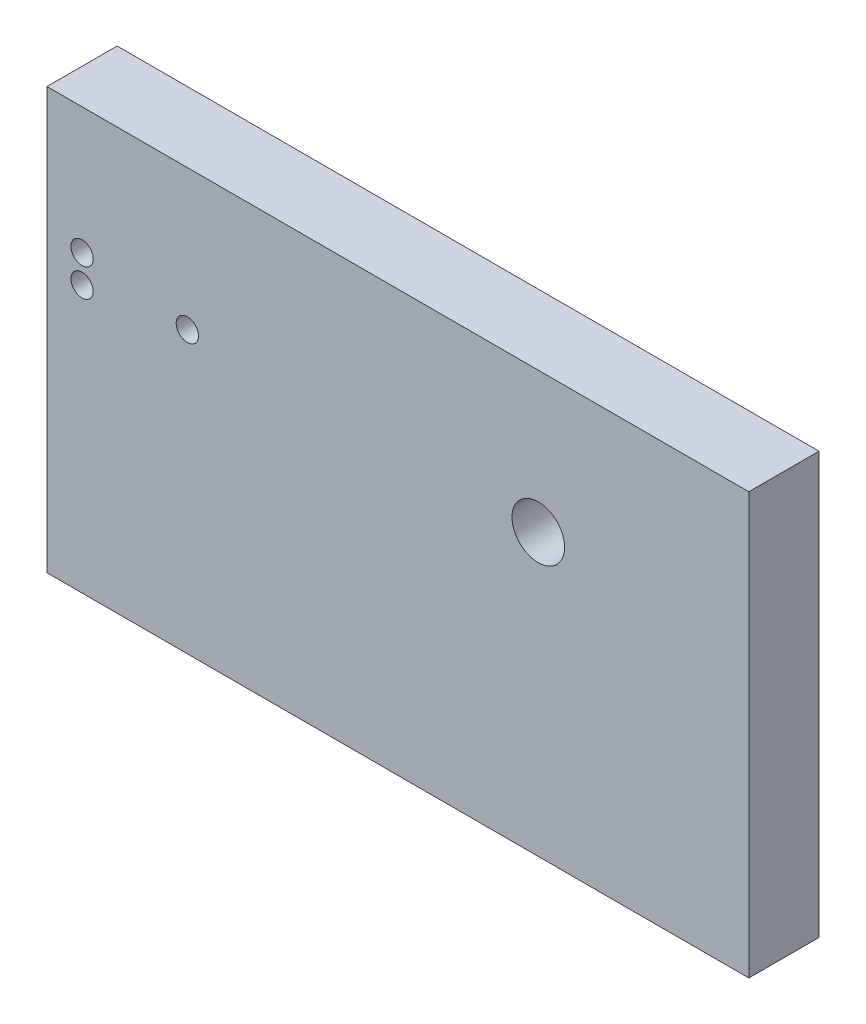
SolidWorks part; units mm, degrees
ref_plane "Front Plane" through (0, 0, 0) normal (0, 0, 1) x (1, 0, 0)
ref_plane "Top Plane" through (0, 0, 0) normal (0, 1, 0) x (1, 0, 0)
ref_plane "Right Plane" through (0, 0, 0) normal (1, 0, 0) x (0, 0, -1)
sketch "Sketch1" plane through (0, 0, 0) normal (0, 0, 1) x (1, 0, 0)
  line L1 (0, 0) -> (127, 0)
  line L2 (0, 0) -> (0, 76.2)
  line L3 (0, 76.2) -> (127, 76.2)
  line L4 (127, 0) -> (127, 76.2)
  dimension "D1" = 127
  dimension "D2" = 76.2
extrude "Boss-Extrude1" add sketch "Sketch1" along normal blind 12.7 contours L2 L1 L4 L3
hole_wizard "1/32 (0.159) Diameter Hole1" positions "Sketch5" profile "Sketch6" hole size "1/32" standard "ANSI Inch" end condition through all
sketch "Sketch5" plane through (0, 0, 12.7) normal (0, 0, 1) x (1, 0, 0)
  line L0 (0, 0) -> (0, 76.2) construction
  line L1 (0, 0) -> (127, 0) construction
  point P0 (25.4, 50.8)
  dimension "D1" = 25.4
  dimension "D2" = 50.8
sketch "Sketch6" plane through (25.4, 50.8, 12.7) normal (1, 0, 0) x (0, -1, 0)
  line L0 (0, 0) -> (0, 12.7)
  line L1 (0, 12.7) -> (2.0193, 12.7)
  line L2 (2.0193, 12.7) -> (2.0193, 0)
  line L5 (2.0193, 0) -> (0, 0)
  line L11 (0, -6.35) -> (0, 107.95) construction
  dimension "Thru Hole Dia." = 4.0386
  dimension "Thru Hole Depth" = 12.7
hole_wizard "#10-32 Tapped Hole1" positions "Sketch9" profile "Sketch10" tap size "#10-32" standard "ANSI Inch"
sketch "Sketch9" plane through (0, 0, 0) normal (0, -1, 0) x (-1, 0, 0)
  line L0 (0, -12.7) -> (-127, -12.7) construction
  line L1 (-19.05, -6.35) -> (-107.95, -6.35) construction
  line L3 (-63.5, -12.7) -> (-63.5, 0) construction
  line L4 (0, 0) -> (-127, 0) construction
  point P0 (-19.05, -6.35)
  point P2 (-107.95, -6.35)
  point P21 (-63.5, -6.35)
  dimension "D1" = 6.35
  dimension "D2" = 88.9
sketch "Sketch10" plane through (19.05, 0, 6.35) normal (1, 0, 0) x (0, 0, -1)
  line L0 (0, 0) -> (0, 13.9133)
  line L1 (0, 13.9133) -> (2.0193, 12.7)
  line L2 (2.0193, 12.7) -> (2.0193, 0)
  line L5 (2.0193, 0) -> (0, 0)
  line L10 (0, 13.9133) -> (-2.0193, 12.7) construction
  line L11 (0, -6.35) -> (0, 107.95) construction
  dimension "Tap Drill Dia." = 4.0386
  dimension "Tap Drill Depth" = 12.7
  dimension "Drill Angle" = 118
cosmetic thread "Hole Thread3" parameters "D1"=12.7, "D2"=4.826
cosmetic thread "Hole Thread4" parameters "D1"=12.7, "D2"=4.826
hole_wizard "3/8 (0.375) Diameter Hole1" positions "Sketch14" profile "Sketch15" hole size "3/8" standard "ANSI Inch" end condition through all
sketch "Sketch14" plane through (0, 0, 12.7) normal (0, 0, 1) x (1, 0, 0)
  line L0 (0, 0) -> (127, 0) construction
  line L1 (0, 0) -> (0, 76.2) construction
  point P0 (88.9, 50.8)
  dimension "D1" = 50.8
  dimension "D2" = 88.9
sketch "Sketch15" plane through (88.9, 50.8, 12.7) normal (1, 0, 0) x (0, -1, 0)
  line L0 (0, 0) -> (0, 12.7)
  line L1 (0, 12.7) -> (4.7625, 12.7)
  line L2 (4.7625, 12.7) -> (4.7625, 0)
  line L5 (4.7625, 0) -> (0, 0)
  line L11 (0, -6.35) -> (0, 107.95) construction
  dimension "Thru Hole Dia." = 9.525
  dimension "Thru Hole Depth" = 12.7
hole_wizard "#10-32 Tapped Hole2" positions "Sketch16" profile "Sketch17" tap size "#10-32" standard "ANSI Inch"
sketch "Sketch16" plane through (0, 0, 12.7) normal (0, 0, 1) x (1, 0, 0)
  line L0 (0, 0) -> (0, 76.2) construction
  line L1 (0, 0) -> (127, 0) construction
  point P0 (6.35, 48.26)
  dimension "D1" = 6.35
  dimension "D2" = 48.26
sketch "Sketch17" plane through (6.35, 48.26, 12.7) normal (1, 0, 0) x (0, -1, 0)
  line L0 (0, 0) -> (0, 15.6913)
  line L1 (0, 15.6913) -> (2.0193, 14.478)
  line L2 (2.0193, 14.478) -> (2.0193, 0)
  line L5 (2.0193, 0) -> (0, 0)
  line L10 (0, 15.6913) -> (-2.0193, 14.478) construction
  line L11 (0, -6.35) -> (0, 107.95) construction
  dimension "Tap Drill Dia." = 4.0386
  dimension "Tap Drill Depth" = 14.478
  dimension "Drill Angle" = 118
cosmetic thread "Hole Thread5" parameters "D1"=9.652, "D2"=4.826
hole_wizard "#21 (0.159) Diameter Hole1" positions "Sketch18" profile "Sketch19" hole size "#21" standard "ANSI Inch"
sketch "Sketch18" plane through (0, 0, 12.7) normal (0, 0, 1) x (1, 0, 0)
  line L0 (0, 0) -> (0, 76.2) construction
  line L1 (0, 0) -> (127, 0) construction
  point P0 (6.35, 53.34)
  dimension "D1" = 6.35
  dimension "D2" = 53.34
sketch "Sketch19" plane through (6.35, 53.34, 12.7) normal (1, 0, 0) x (0, -1, 0)
  line L0 (0, 0) -> (0, 15.6913)
  line L1 (0, 15.6913) -> (2.0193, 14.478)
  line L2 (2.0193, 14.478) -> (2.0193, 0)
  line L5 (2.0193, 0) -> (0, 0)
  line L10 (0, 15.6913) -> (-2.0193, 14.478) construction
  line L11 (0, -6.35) -> (0, 107.95) construction
  dimension "Hole Dia." = 4.0386
  dimension "Hole Depth" = 14.478
  dimension "Drill Angle" = 118
